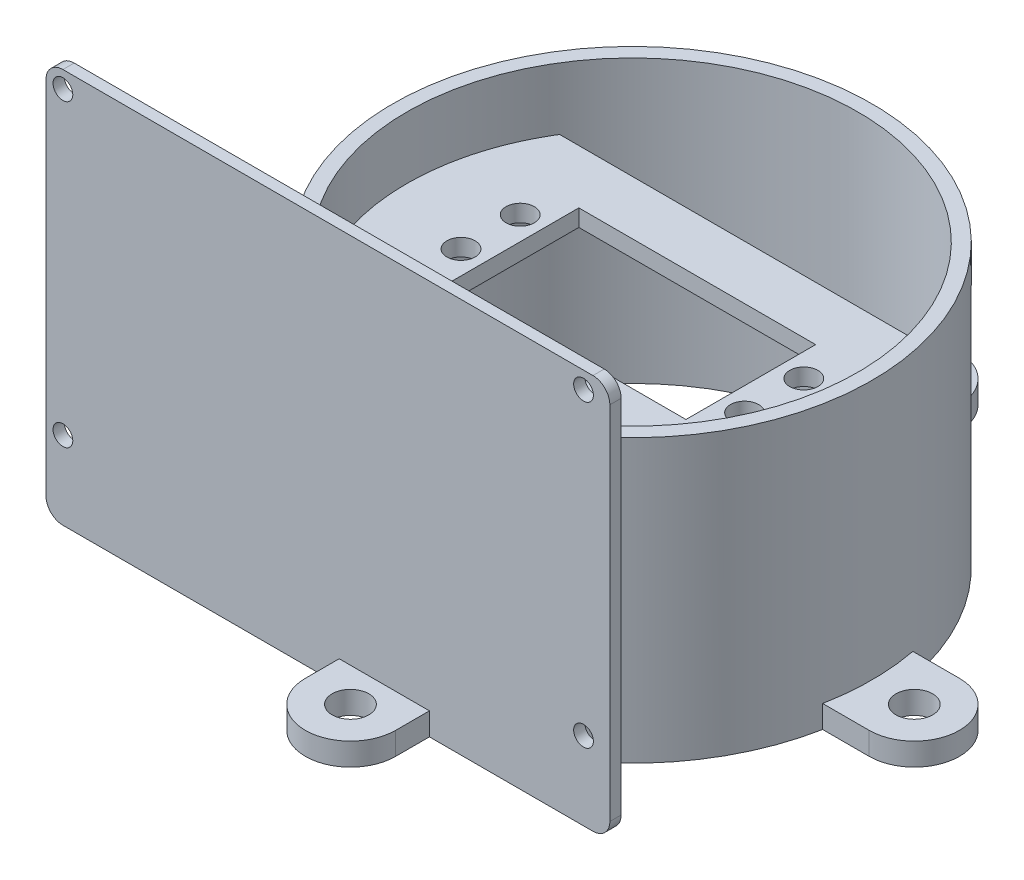
SolidWorks part; units mm, degrees
ref_plane "Front Plane" through (0, 0, 0) normal (0, 0, 1) x (1, 0, 0)
ref_plane "Top Plane" through (0, 0, 0) normal (0, 1, 0) x (1, 0, 0)
ref_plane "Right Plane" through (0, 0, 0) normal (1, 0, 0) x (0, 0, -1)
sketch "Sketch1" plane through (0, 0, 0) normal (0, 1, 0) x (1, 0, 0)
  circle A0 centre (0, 0) radius 40
  circle A1 centre (0, 0) radius 42.5
  dimension "D1" = 80
  dimension "D2" = 85
extrude "Boss-Extrude1" add sketch "Sketch1" along normal blind 50
sketch "Sketch2" plane through (0, 0, 0) normal (0, -1, 0) x (1, 0, 0)
  line L0 (42.5, 0) -> (50.0003, 0) construction
  line L1 (41.7403, 8) -> (50.0003, 8)
  line L2 (41.7403, -8) -> (50.0003, -8)
  circle A0 centre (0, 0) radius 42.5 construction
  circle A1 centre (50.0003, 0) radius 3.25
  arc A2 (50.0003, -8) -> (50.0003, 8) centre (50.0003, 0) ccw
  circle M3 centre (0, 0) radius 42.5
  dimension "D2" = 6.5
  dimension "D4" = 16
  dimension "D1" = 8.26
  dimension "D3" = 8
extrude "Boss-Extrude2" add sketch "Sketch2" against normal blind 4 contours L2 A2 L1 A1 M3 region at (45.8703, 0, 7.7719)
pattern_circular "CirPattern1" count 4 over 360 about axis through (0, 0, 0) along (0, 1, 0) of "Boss-Extrude2"
ref_plane "Plane1" through (0, 36, 0) normal (0, 1, 0) x (1, 0, 0)
sketch "Sketch4" plane through (0, 36, 0) normal (0, 1, 0) x (1, 0, 0)
  line L5 (34, -21.0713) -> (-34, -21.0713)
  line L7 (34, 21.0713) -> (-34, 21.0713)
  line L9 (34, -21.0713) -> (-34, 21.0713) construction
  line L10 (34, 21.0713) -> (-34, -21.0713) construction
  circle A3 centre (0, 0) radius 40 construction
  arc A4 (-34, 21.0713) -> (-34, -21.0713) centre (0, 0) ccw
  arc A5 (34, -21.0713) -> (34, 21.0713) centre (0, 0) ccw
  point P0 (0, 0)
  dimension "D1" = 68
extrude "Boss-Extrude3" add sketch "Sketch4" along normal blind 3 separate body
sketch "Sketch3" plane through (0, 39, 0) normal (0, 1, 0) x (1, 0, 0)
  line L0 (-25.15, 5.25) -> (25.15, 5.25) construction
  line L1 (-25.15, 5.25) -> (-25.15, -5.25) construction
  line L2 (-25.15, -5.25) -> (25.15, -5.25) construction
  line L3 (25.15, 5.25) -> (25.15, -5.25) construction
  line L4 (-25.15, 5.25) -> (25.15, -5.25) construction
  line L5 (25.15, -5.25) -> (25.15, 5.25) construction
  line L6 (25.15, 5.25) -> (-25.15, -5.25) construction
  line L7 (21, -11.5) -> (-21, -11.5)
  line L8 (21, -11.5) -> (21, 11.5)
  line L9 (21, 11.5) -> (-21, 11.5)
  line L10 (-21, -11.5) -> (-21, 11.5)
  line L11 (21, -11.5) -> (-21, 11.5) construction
  line L12 (21, 11.5) -> (-21, -11.5) construction
  circle A0 centre (25.15, 5.25) radius 2.5
  circle A1 centre (25.15, -5.25) radius 2.5
  circle A2 centre (-25.15, -5.25) radius 2.5
  circle A3 centre (-25.15, 5.25) radius 2.5
  circle A4 centre (0, 0) radius 12.5 construction
  dimension "D1" = 5
  dimension "D4" = 25
  dimension "D2" = 10.5
  dimension "D3" = 50.3
  dimension "D5" = 42
  dimension "D6" = 23
extrude "Cut-Extrude1" cut sketch "Sketch3" against normal up to next (3 mm away)
sketch "Sketch5" plane through (0, 0, 0) normal (0, 0, 1) x (1, 0, 0)
  line L0 (0, 0) -> (0, 36) construction
  line L1 (-60, 70) -> (40, 70)
  line L2 (-60, 70) -> (-60, 0)
  line L3 (-60, 0) -> (40, 0)
  line L4 (40, 70) -> (40, 0)
  line L5 (46.75, 36) -> (-46.75, 36) construction
  line L6 (-10, 0) -> (-10, 70) construction
  circle A0 centre (-57, 67) radius 1.75
  circle A1 centre (35.33, 67) radius 1.75
  circle A2 centre (-57, 13.85) radius 1.75
  circle A3 centre (35.33, 13.85) radius 1.75
  dimension "D3" = 3.5
  dimension "D4" = 92.33
  dimension "D5" = 3
  dimension "D6" = 3
  dimension "D8" = 53.15
  dimension "D1" = 100
  dimension "D2" = 70
  dimension "D9" = 10
  dimension "D7" = 2
extrude "Boss-Extrude4" add sketch "Sketch5" along normal blind 2 from offset 42
fillet "Fillet1" radius 3 4 edges at (40, 70, 43) (-60, 70, 43) (40, 0, 43) (-60, 0, 43)
